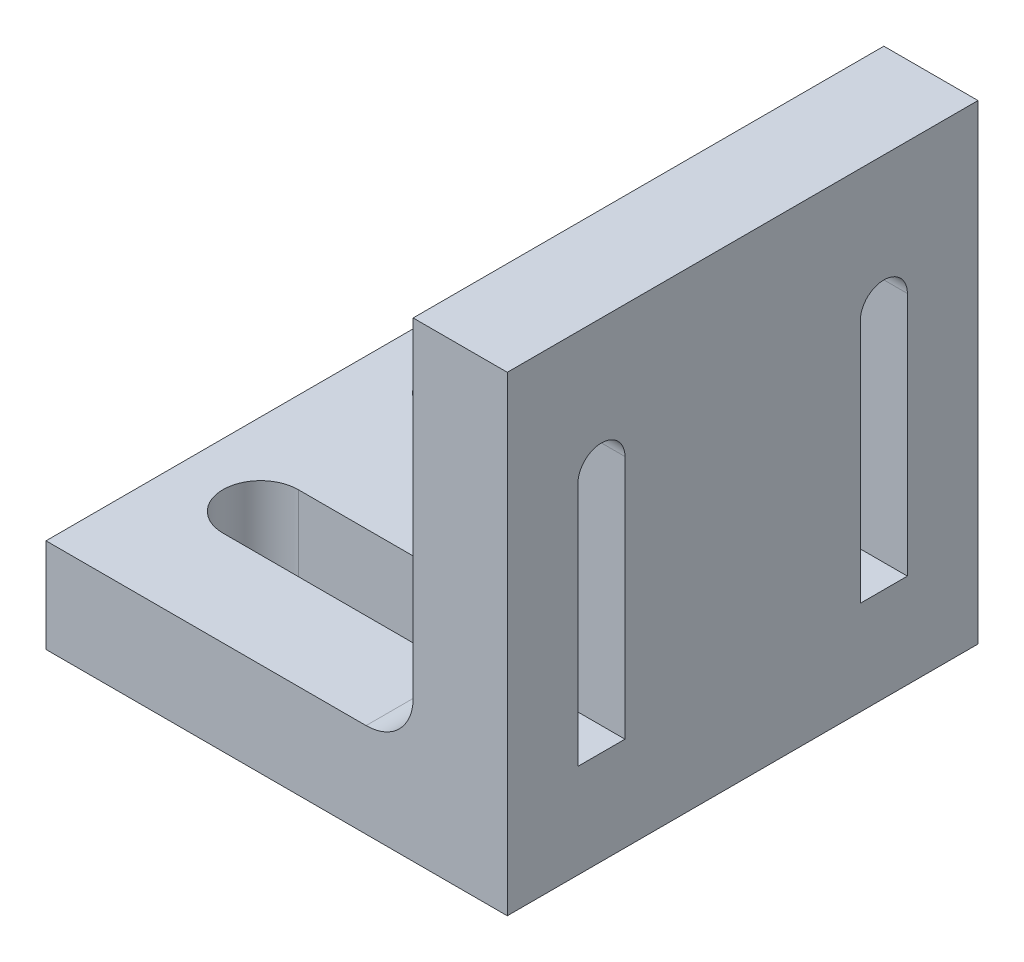
SolidWorks part; units mm, degrees
ref_plane "Front Plane" through (0, 0, 0) normal (0, 0, 1) x (1, 0, 0)
ref_plane "Top Plane" through (0, 0, 0) normal (0, 1, 0) x (1, 0, 0)
ref_plane "Right Plane" through (0, 0, 0) normal (1, 0, 0) x (0, 0, -1)
sketch "Sketch1" plane through (0, 0, 0) normal (0, 0, 1) x (1, 0, 0)
  line L0 (0, 50) -> (0, 0)
  line L1 (0, 0) -> (-49, 0)
  line L2 (-10, 50) -> (-10, 10)
  line L3 (-10, 10) -> (-49, 10)
  line L4 (0, 50) -> (-10, 50)
  line L5 (-49, 0) -> (-49, 10)
  dimension "D1" = 49
  dimension "D2" = 50
  dimension "D3" = 10
extrude "Boss-Extrude1" add sketch "Sketch1" along normal blind 50
sketch "Sketch2" plane through (0, 0, 0) normal (1, 0, 0) x (0, 0, -1)
  line L1 (-7.5, 11) -> (-7.5, 36) construction
  line L2 (-12.5, 36) -> (-12.5, 11) construction
  line L5 (-7.5, 10) -> (-7.5, 36)
  line L6 (-12.5, 36) -> (-12.5, 10)
  line L8 (-50, 10) -> (0, 10) construction
  line L10 (-12.5, 10) -> (-7.5, 10)
  line L11 (-25, 50) -> (-25, 10) construction
  line L12 (-50, 50) -> (0, 50) construction
  line L13 (-50, 10) -> (0, 10) construction
  line L14 (-37.5, 10) -> (-42.5, 10)
  line L15 (-37.5, 36) -> (-37.5, 10)
  line L16 (-42.5, 10) -> (-42.5, 36)
  arc A0 (-7.5, 36) -> (-12.5, 36) centre (-10, 36) ccw
  arc A1 (-42.5, 36) -> (-37.5, 36) centre (-40, 36) cw
extrude "Cut-Extrude1" cut sketch "Sketch2" against normal blind 17
sketch "Sketch3" plane through (0, 10, 0) normal (0, 1, 0) x (1, 0, 0)
  line L0 (-40.3084, -14.1037) -> (-17.9476, -14.1037) construction
  line L1 (-40.3084, -10.1037) -> (-17.9476, -10.1037)
  line L2 (-40.3084, -18.1037) -> (-17.9476, -18.1037)
  line L3 (-49, -25) -> (-10, -25) construction
  line L6 (-49, -50) -> (-49, 0) construction
  line L9 (-10, -50) -> (-10, 0) construction
  line L10 (-40.3084, -35.8963) -> (-17.9476, -35.8963) construction
  line L11 (-40.3084, -39.8963) -> (-17.9476, -39.8963)
  line L12 (-40.3084, -31.8963) -> (-17.9476, -31.8963)
  arc A0 (-40.3084, -10.1037) -> (-40.3084, -18.1037) centre (-40.3084, -14.1037) ccw
  arc A1 (-17.9476, -18.1037) -> (-17.9476, -10.1037) centre (-17.9476, -14.1037) ccw
  arc A4 (-40.3084, -39.8963) -> (-40.3084, -31.8963) centre (-40.3084, -35.8963) cw
  arc A5 (-17.9476, -31.8963) -> (-17.9476, -39.8963) centre (-17.9476, -35.8963) cw
  point P2 (-29.128, -14.1037)
  point P15 (-29.128, -35.8963)
  dimension "D1" = 4
extrude "Cut-Extrude2" cut sketch "Sketch3" against normal blind 17
fillet "Fillet1" radius 5 3 edges at (-10, 10, 46.25) (-10, 10, 3.75) (-10, 10, 25)
